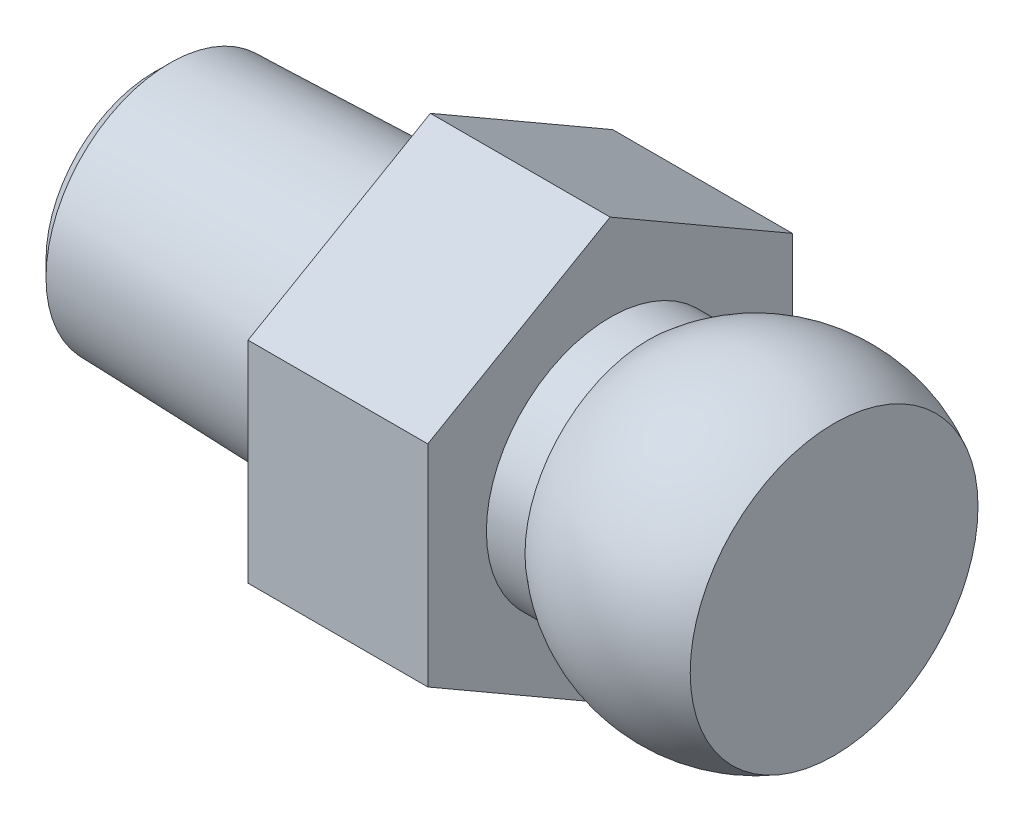
SolidWorks part; units mm, degrees
ref_plane "前视" through (0, 0, 0) normal (0, 0, 1) x (1, 0, 0)
ref_plane "上视" through (0, 0, 0) normal (0, 1, 0) x (1, 0, 0)
ref_plane "右视" through (0, 0, 0) normal (1, 0, 0) x (0, 0, -1)
sketch "草图1" plane through (0, 0, 0) normal (0, 0, 1) x (1, 0, 0)
  line L0 (0, 0) -> (0, 4.1581)
  line L1 (0, 4.1581) -> (0.5997, 4.7578)
  line L2 (0.5997, 4.7578) -> (10.6, 5.07)
  line L3 (10.6, 5.07) -> (10.6, 12)
  line L4 (10.6, 12) -> (17.5, 12)
  line L5 (17.5, 12) -> (17.5, 4.75)
  line L6 (17.5, 4.75) -> (18.982, 4.75)
  line L7 (26.1, 5.5245) -> (26.1, 0)
  line L8 (26.1, 0) -> (0, 0)
  line L9 (26.1, 0) -> (0, 0) construction
  arc A0 (18.982, 4.75) -> (26.1, 5.5245) centre (23.1, 0) cw
revolve "旋转1" add sketch "草图1" angle 360 about L9 reverse direction yes
ref_plane "基准面1" through (10.6, 0, 0) normal (-1, 0, 0) x (0, 0, 1)
sketch "草图2" plane through (10.6, 0, 0) normal (-1, 0, 0) x (0, 0, 1)
  line L0 (0, -8.0829) -> (7, -4.0415)
  line L1 (7, -4.0415) -> (7, 4.0415)
  line L2 (7, 4.0415) -> (0, 8.0829)
  line L3 (0, 8.0829) -> (-7, 4.0415)
  line L4 (-7, 4.0415) -> (-7, -4.0415)
  line L5 (-7, -4.0415) -> (0, -8.0829)
  circle A0 centre (0, 0) radius 14
extrude "切除-拉伸1" cut sketch "草图2" against normal blind 6.9
ref_plane "基准面2" through (0, 0, 0) normal (0, 0, 1) x (1, 0, 0)
ref_plane "to_hose XY" through (0, 0, 0) normal (0, 0, 1) x (1, 0, 0)
ref_plane "to_hose XZ" through (0, 0, 0) normal (0, -1, 0) x (-1, 0, 0)
ref_plane "to_hose YZ" through (23.1, 0, 0) normal (1, 0, 0) x (0, 0, -1)
ref_axis "to_hose X" through (-80.9, 0, 0) along (1, 0, 0)
ref_axis "to_hose Y" through (23.1, -50, 0) along (0, 1, 0)
ref_axis "to_hose Z" through (23.1, 0, 80.9) along (0, 0, -1)
sketch3d "to_hose"
  point P0 (23.1, 0, 0)
